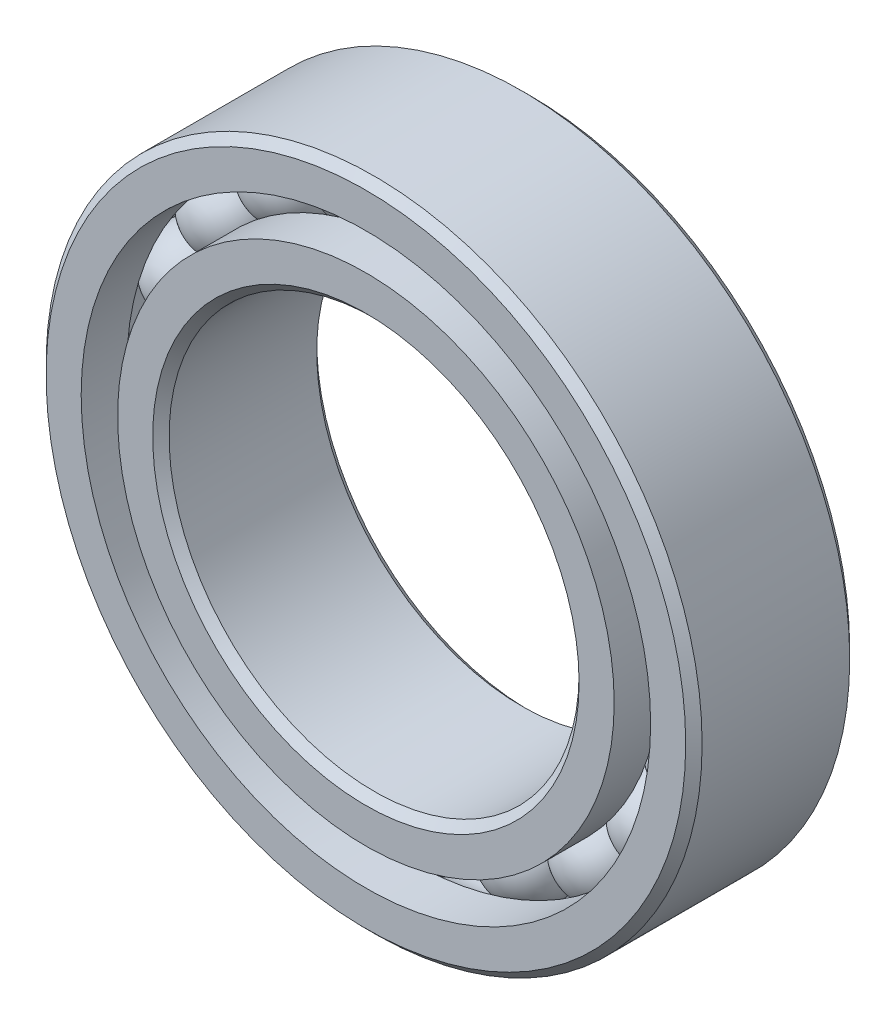
SolidWorks part; units mm, degrees
ref_plane "Front Plane" through (0, 0, 0) normal (0, 0, 1) x (1, 0, 0)
ref_plane "Top Plane" through (0, 0, 0) normal (0, 1, 0) x (1, 0, 0)
ref_plane "Right Plane" through (0, 0, 0) normal (1, 0, 0) x (0, 0, -1)
sketch "Sketch1" plane through (0, 0, 0) normal (1, 0, 0) x (0, 0, -1)
  line L0 (-1, 0) -> (1, 0) construction
  line L1 (0, 4) -> (0, -4) construction
  line L2 (0.9, 4) -> (-0.9, 4) construction
  line L3 (-0.9, 4) -> (-1, 3.9) construction
  line L4 (-1, 3.9) -> (-1, 3.4722) construction
  line L5 (-1, 3.4722) -> (-0.4444, 3.4722) construction
  line L6 (1, 3.4722) -> (0.4444, 3.4722) construction
  line L7 (1, 3.9) -> (1, 3.4722) construction
  line L8 (0.9, 4) -> (1, 3.9) construction
  line L9 (0, 4) -> (0, 3.25) construction
  line L10 (0, 3.25) -> (0, 2.5) construction
  arc A0 (-0.4444, 3.4722) -> (0.4444, 3.4722) centre (0, 3.25) cw construction
  arc A1 (-0.4444, 3.4722) -> (0.4444, 3.4722) centre (0, 3.25) ccw construction
  point P14 (0, 2.5)
  point P15 (0, -2.5)
  dimension "Width" = 2
  dimension "OD" = 8
  dimension "D1" = 45
  dimension "D2" = 0.1
  dimension "D3" = 0.8889
  dimension "Shaft Dia" = 5
  dimension "D4" = 0.2222
sketch "Sketch2" plane through (0, 0, 0) normal (1, 0, 0) x (0, 0, -1)
  line L0 (-1, 3.0278) -> (-0.4444, 3.0278)
  line L2 (-1, 3.0278) -> (-1, 2.6)
  line L3 (-1, 2.6) -> (-0.9, 2.5)
  line L4 (-0.9, 2.5) -> (0.9, 2.5)
  line L5 (0, 4) -> (0, -4) construction
  line L6 (0, 2.5) -> (0, 2.7531) construction
  line L7 (0, 2.7531) -> (0, 2.5) construction
  line L9 (-1, 3.9) -> (-1, 3.4722) construction
  line L10 (1, 3.0278) -> (0.4444, 3.0278)
  line L11 (1, 3.0278) -> (1, 2.6)
  line L12 (1, 2.6) -> (0.9, 2.5)
  line L13 (0.9, 4) -> (1, 3.9) construction
  line L14 (1, 3.9) -> (1, 3.4722) construction
  line L15 (1, 3.4722) -> (0.4444, 3.4722) construction
  line L16 (-1, 3.4722) -> (-0.4444, 3.4722) construction
  line L17 (0.9, 4) -> (-0.9, 4) construction
  line L18 (-0.9, 4) -> (-1, 3.9) construction
  line L19 (0.9, 4) -> (1, 3.9)
  line L20 (1, 3.9) -> (1, 3.4722)
  line L21 (1, 3.4722) -> (0.4444, 3.4722)
  line L22 (-1, 3.4722) -> (-0.4444, 3.4722)
  line L23 (-1, 3.9) -> (-1, 3.4722)
  line L24 (0.9, 4) -> (-0.9, 4)
  line L25 (-0.9, 4) -> (-1, 3.9)
  line L26 (-1, 2.6) -> (-0.9, 2.6) construction
  line L27 (-0.9, 2.6) -> (-0.9, 2.5) construction
  arc A0 (-0.4444, 3.0278) -> (0.4444, 3.0278) centre (0, 3.25) ccw
  arc A1 (0.4444, 3.4722) -> (-0.4444, 3.4722) centre (0, 3.25) ccw construction
  circle A2 centre (0, 3.25) radius 0.4969 construction
  arc A3 (-0.4444, 3.4722) -> (0.4444, 3.4722) centre (0, 3.25) cw
  dimension "D1" = 0.1
revolve "Revolve1" add sketch "Sketch2" angle 360 about L0
sketch "Sketch3" plane through (0, 0, 0) normal (1, 0, 0) x (0, 0, -1)
  line L0 (-0.4969, 3.25) -> (0.4969, 3.25)
  line L1 (0, 3.25) -> (0, 0) construction
  circle A1 centre (0, 3.25) radius 0.4969 construction
  arc A2 (-0.4969, 3.25) -> (0.4969, 3.25) centre (0, 3.25) cw
  arc A3 (0.4444, 3.4722) -> (-0.4444, 3.4722) centre (0, 3.25) ccw construction
  dimension "D1" = 0.9938
  dimension "D2" = 3.25
revolve "Revolve2" add sketch "Sketch3" angle 360 about L0
ref_axis "Axis1" through (0, 0, -1) along (0, 0, 1)
pattern_circular "CirPattern1" count 20 every 18 about axis through (0, 0, -1) along (0, 0, 1) of bodies 104
sketch "Sketch6" plane through (0, 0, 0) normal (0, 1, 0) x (1, 0, 0)
  point P0 (4, -1)
  point P1 (4, 1)
equation "\"D2@Sketch1\" = \"Width@Sketch1\"*.05"
equation "\"D3@Sketch1\" = \"Width@Sketch1\"/2.25"
equation "\"D4@Sketch1\" = \"D3@Sketch1\"/4"
equation "\"Balls@CirPattern1\"=\"D2@Sketch3\"*2*pi/\"D1@Sketch3\"-1"
equation "\"D2@CirPattern1\" = 360/\"Balls@CirPattern1\""
equation "\"D1@Sketch2\"=\"D2@Sketch1\""
equation "\"D1@Sketch6\"=\"Width@Sketch1\""
